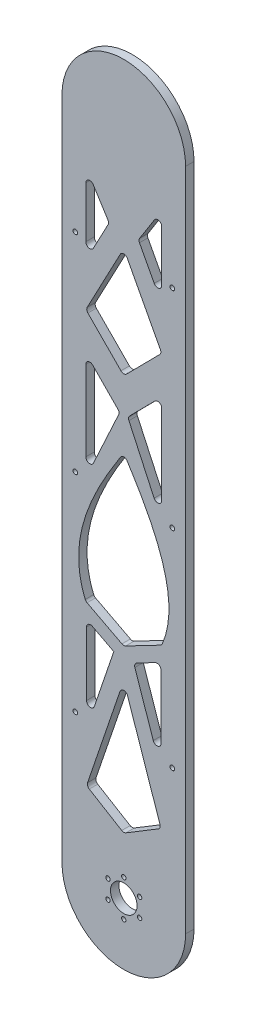
SolidWorks part; units mm, degrees
material "1060 Alloy"
ref_plane "Front Plane" through (0, 0, 0) normal (0, 0, 1) x (1, 0, 0)
ref_plane "Top Plane" through (0, 0, 0) normal (0, 1, 0) x (1, 0, 0)
ref_plane "Right Plane" through (0, 0, 0) normal (1, 0, 0) x (0, 0, -1)
sketch "Sketch2" plane through (0, 0, 0) normal (0, 0, 1) x (1, 0, 0)
  line L0 (0, 0) -> (0, 500) construction
  line L1 (-46.5, 0) -> (-46.5, 500)
  line L2 (46.5, 0) -> (46.5, 500)
  arc A0 (-46.5, 0) -> (46.5, 0) centre (0, 0) ccw
  arc A1 (46.5, 500) -> (-46.5, 500) centre (0, 500) ccw
  circle A2 centre (0, 500) radius 37.25 construction
  circle A3 centre (0, 0) radius 10
  circle A4 centre (0, 13.75) radius 1.65
  circle A5 centre (0, 0) radius 13.75 construction
  circle A6 centre (11.9078, 6.875) radius 1.65
  circle A7 centre (11.9078, -6.875) radius 1.65
  circle A8 centre (0, -13.75) radius 1.65
  circle A9 centre (-11.9078, -6.875) radius 1.65
  circle A10 centre (-11.9078, 6.875) radius 1.65
  point P3 (0, 250)
  point P27 (0, 0)
  dimension "D2" = 74.5
  dimension "D4" = 20
  dimension "D5" = 3.3
  dimension "D6" = 27.5
  dimension "D3" = 46.5
  dimension "D1" = 500
  dimension "D7" = 6
extrude "Boss-Extrude1" add sketch "Sketch2" along normal blind 6.35
sketch "Sketch4" plane through (0, 0, 6.35) normal (0, 0, 1) x (1, 0, 0)
  line L0 (0, 500) -> (0, 999.1647) construction
  line L29 (46.5, 500) -> (-46.5, 500) construction
  line L31 (28.0053, 59.376) -> (0, 42.4117)
  line L32 (0, 141.6934) -> (28.0053, 59.376)
  line L33 (-28.0053, 59.376) -> (0, 141.6934)
  line L34 (0, 42.4117) -> (-28.0053, 59.376)
  line L35 (-7.5, 156.9059) -> (-28.0053, 96.6336)
  line L36 (-28.0053, 167.5829) -> (-7.5, 156.9059)
  line L37 (-28.0053, 96.6336) -> (-28.0053, 167.5829)
  line L38 (28.0053, 167.5829) -> (7.5, 156.9059)
  line L39 (28.0053, 96.6336) -> (28.0053, 167.5829)
  line L40 (7.5, 156.9059) -> (28.0053, 96.6336)
  line L41 (0, 164.2751) -> (28.5505, 179.1412)
  line L42 (0, 164.2751) -> (-28.5505, 179.1412)
  line L43 (28.5505, 259.5868) -> (3, 314.9383)
  line L44 (28.5505, 340.7931) -> (28.5505, 259.5868)
  line L45 (3, 314.9383) -> (28.5505, 340.7931)
  line L46 (-3, 314.9383) -> (-28.5505, 340.7931)
  line L47 (-28.5505, 259.5868) -> (-3, 314.9383)
  line L48 (-28.5505, 340.7931) -> (-28.5505, 259.5868)
  line L49 (0, 423.1428) -> (-28.5505, 369.2462)
  line L50 (-28.5505, 369.2462) -> (0, 340.3557)
  line L51 (0, 340.3557) -> (28.5505, 369.2462)
  line L52 (0, 423.1428) -> (28.5505, 369.2462)
  line L53 (-28.5505, 462.0952) -> (-28.5505, 401.2902)
  line L54 (-11, 434.4215) -> (-28.5505, 462.0952)
  line L55 (-28.5505, 401.2902) -> (-11, 434.4215)
  line L56 (28.5505, 401.2902) -> (11, 434.4215)
  line L57 (28.5505, 462.0952) -> (28.5505, 401.2902)
  line L58 (11, 434.4215) -> (28.5505, 462.0952)
  arc A0 (46.5, 500) -> (-46.5, 500) centre (0, 500) ccw construction
  arc A1 (46.5, 500) -> (-46.5, 500) centre (0, 500) ccw construction
  spline S2 degree 3 poles (28.5505, 179.1412) (45.3203, 216.9857) (19.4301, 259.7903) (0, 290.0258) knots 0 0 0 0 1 1 1 1
  spline S3 degree 3 poles (-28.5505, 179.1412) (-45.3203, 216.9857) (-19.4301, 259.7903) (0, 290.0258) knots 0 0 0 0 1 1 1 1
extrude "Cut-Extrude1" cut sketch "Sketch4" against normal blind 10
fillet "Fillet3" radius 3 29 edges at (-11, 434.4215, 3.175) (-28.5505, 401.2902, 3.175) (28.5505, 401.2902, 3.175) (11, 434.4215, 3.175) (28.5505, 462.0952, 3.175) (-28.5505, 462.0952, 3.175) (0, 423.1428, 3.175) (-28.5505, 369.2462, 3.175) (28.5505, 369.2462, 3.175) (0, 340.3557, 3.175) (28.5505, 340.7931, 3.175) (-28.5505, 340.7931, 3.175) (-3, 314.9383, 3.175) (3, 314.9383, 3.175) (28.5505, 259.5868, 3.175) (-28.5505, 259.5868, 3.175) (28.5505, 179.1412, 3.175) (0, 290.0258, 3.175) (-28.5505, 179.1412, 3.175) (0, 164.2751, 3.175) (-28.0053, 96.6336, 3.175) (28.0053, 96.6336, 3.175) (7.5, 156.9059, 3.175) (-28.0053, 167.5829, 3.175) (28.0053, 167.5829, 3.175) (0, 141.6934, 3.175) (28.0053, 59.376, 3.175) (-28.0053, 59.376, 3.175) (0, 42.4117, 3.175)
sketch "Sketch5" plane through (0, 0, 6.35) normal (0, 0, 1) x (1, 0, 0)
  line L0 (0, -46.5) -> (108.8395, -46.5) construction
  line L1 (46.5, 100) -> (-46.5, 100) construction
  line L2 (46.5, 0) -> (46.5, 500) construction
  line L3 (-46.5, 500) -> (-46.5, 0) construction
  line L4 (-46.5, 106.35) -> (46.5, 106.35) construction
  line L5 (36.5, 106.35) -> (36.5, 100) construction
  line L6 (0, 106.35) -> (0, 100) construction
  line L7 (-46.5, 256.35) -> (46.5, 256.35) construction
  line L8 (-46.5, 181.35) -> (46.5, 181.35) construction
  line L9 (-46.5, 337.7) -> (46.5, 337.7) construction
  arc A1 (-46.5, 0) -> (46.5, 0) centre (0, 0) ccw construction
  circle A2 centre (36.5, 103.175) radius 1.75
  circle A3 centre (-36.5, 103.175) radius 1.75
  circle A4 centre (36.5, 259.525) radius 1.75
  circle A5 centre (-36.5, 259.525) radius 1.75
  circle A6 centre (36.5, 415.875) radius 1.75
  circle A7 centre (-36.5, 415.875) radius 1.75
  point P18 (36.5, 103.175)
  dimension "D2" = 3.5
  dimension "D1" = 146.5
  dimension "D3" = 10
  dimension "D4" = 6.35
  dimension "D5" = 150
  dimension "D6" = 81.35
  dimension "D7" = 81.35
extrude "Cut-Extrude2" cut sketch "Sketch5" against normal through all
equation "\"L1L\"=500"
equation "\"L1Thick\"=6.35"
equation "\"D1@Sketch2\"=\"L1L\""
equation "\"Harm-Drive-Outer\"=74.5"
equation "\"D2@Sketch2\"=\"Harm-Drive-Outer\""
equation "\"D1@Boss-Extrude1\"=\"L1Thick\""
